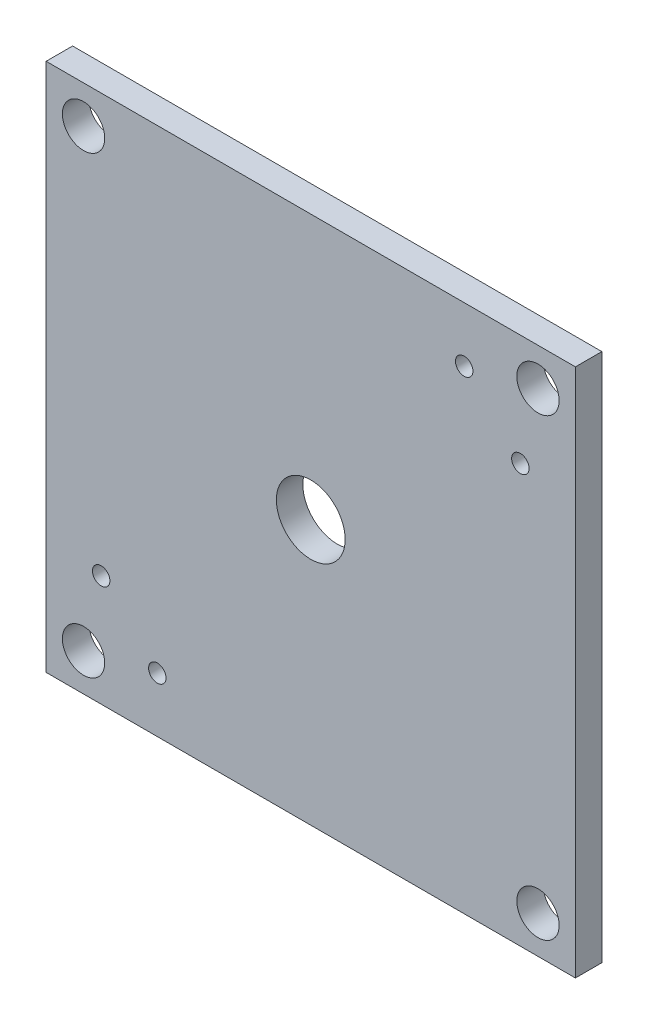
SolidWorks part; units mm, degrees
ref_plane "Front Plane" through (0, 0, 0) normal (0, 0, 1) x (1, 0, 0)
ref_plane "Top Plane" through (0, 0, 0) normal (0, 1, 0) x (1, 0, 0)
ref_plane "Right Plane" through (0, 0, 0) normal (1, 0, 0) x (0, 0, -1)
sketch "Sketch1" plane through (0, 0, 0) normal (0, 0, 1) x (1, 0, 0)
  line L1 (-50, -50) -> (50, -50)
  line L2 (-50, -50) -> (-50, 50)
  line L3 (-50, 50) -> (50, 50)
  line L4 (50, -50) -> (50, 50)
  line L5 (-50, -50) -> (50, 50) construction
  line L6 (-50, 50) -> (50, -50) construction
  point P0 (0, 0)
  dimension "D1" = 100
  dimension "D2" = 100
extrude "MainBody" add sketch "Sketch1" along normal blind 5
sketch "Sketch2" plane through (0, 0, 5) normal (0, 0, 1) x (1, 0, 0)
  line L0 (0, 0) -> (42.9289, 42.9289) construction
  line L1 (42.9289, 42.9289) -> (50, 50) construction
  line L2 (0, 0) -> (42.9289, -42.9289) construction
  line L3 (42.9289, -42.9289) -> (50, -50) construction
  line L4 (0, 0) -> (-42.9289, -42.9289) construction
  line L5 (-42.9289, -42.9289) -> (-50, -50) construction
  line L6 (0, 0) -> (-42.9289, 42.9289) construction
  line L7 (-42.9289, 42.9289) -> (-50, 50) construction
  circle A0 centre (0, 0) radius 6.5
  circle A1 centre (-42.9289, -42.9289) radius 4
  circle A2 centre (42.9289, -42.9289) radius 4
  circle A3 centre (42.9289, 42.9289) radius 4
  circle A4 centre (-42.9289, 42.9289) radius 4
  dimension "D1" = 13
  dimension "D2" = 8
  dimension "D3" = 10
extrude "Bearing&BushingHoles" cut sketch "Sketch2" against normal through all
hole_wizard "M4 Tapped Hole1" positions "3DSketch1" profile "Sketch4" tap size "M4" standard "ISO" end condition through all
sketch3d "3DSketch1"
  line L0 (0, 0, 0) -> (34.2947, 34.2947, 0) construction
  line L1 (34.2947, 34.2947, 0) -> (28.9914, 39.598, 0) construction
  line L3 (34.2947, 34.2947, 0) -> (39.598, 28.9914, 0) construction
  line L5 (0, 0, 0) -> (-34.2947, -34.2947, 0) construction
  line L6 (-34.2947, -34.2947, 0) -> (-39.598, -28.9914, 0) construction
  line L8 (-34.2947, -34.2947, 0) -> (-28.9914, -39.598, 0) construction
  line L12 (34.2947, 34.2947, 0) -> (42.9289, 42.9289, 0) construction
  line L14 (-34.2947, -34.2947, 0) -> (-42.9289, -42.9289, 0) construction
  circle A0 centre (0, 0, 0) radius 6.5 construction
  circle A1 centre (0, 0, 0) radius 6.5 construction
  circle A6 centre (42.9289, 42.9289, 0) radius 4 construction
  circle A7 centre (-42.9289, -42.9289, 0) radius 4 construction
  circle A8 centre (42.9289, 42.9289, 0) radius 4
  circle A9 centre (-42.9289, -42.9289, 0) radius 4
  point P0 (-39.598, -28.9914, 0)
  point P2 (-28.9914, -39.598, 0)
  point P4 (28.9914, 39.598, 0)
  point P6 (39.598, 28.9914, 0)
  point P19 (0, 0, 6.5)
  point P21 (0, 0, 6.5)
  point P45 (42.9289, 42.9289, 4)
  point P48 (-42.9289, -42.9289, 4)
  point P50 (42.9289, 42.9289, 4)
  point P52 (-42.9289, -42.9289, 4)
  dimension "D1" = 15
  dimension "D2" = 97
sketch "Sketch4" plane through (-39.598, -28.9914, 0) normal (1, 0, 0) x (0, 1, 0)
  line L0 (0, 0) -> (0, 5)
  line L1 (0, 5) -> (1.65, 5)
  line L2 (1.65, 5) -> (1.65, 0)
  line L5 (1.65, 0) -> (0, 0)
  line L11 (0, -6.35) -> (0, 107.95) construction
  dimension "Thru Tap Drill Dia." = 3.3
  dimension "Thru Tap Drill Depth" = 5
cosmetic thread "Hole Thread1" parameters "D2"=4
cosmetic thread "Hole Thread2" parameters "D2"=4
cosmetic thread "Hole Thread3" parameters "D2"=4
cosmetic thread "Hole Thread4" parameters "D2"=4
